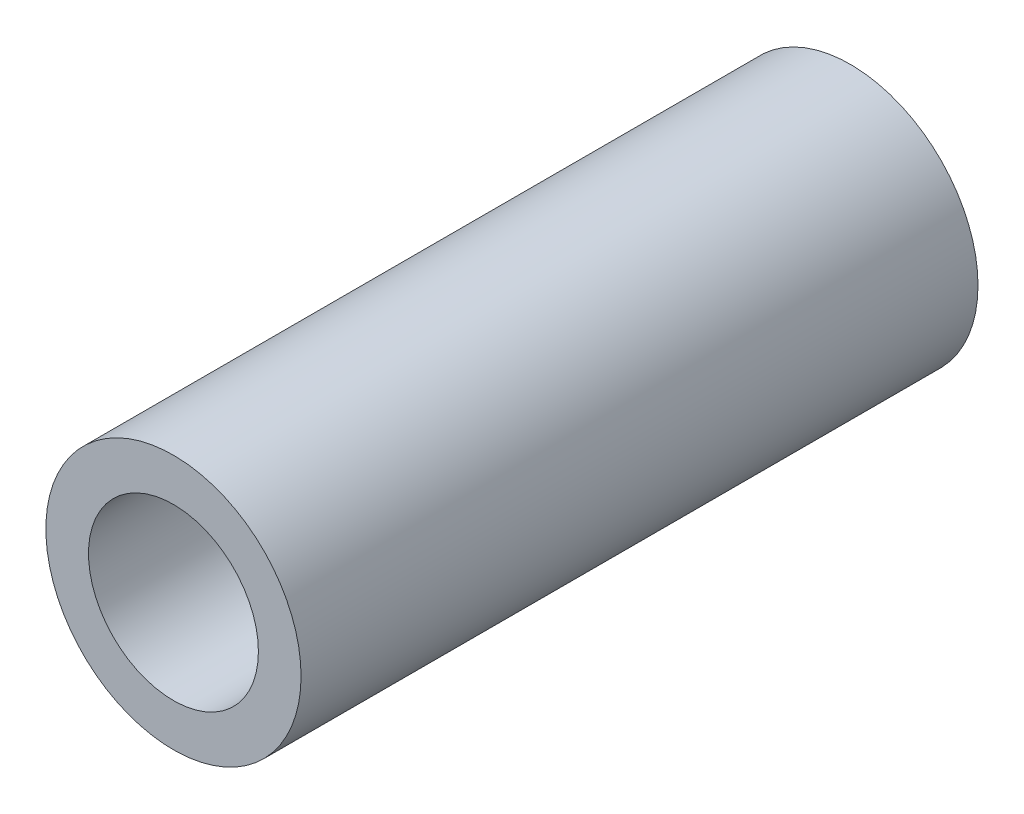
SolidWorks part; units mm, degrees
ref_plane "Front Plane" through (0, 0, 0) normal (0, 0, 1) x (1, 0, 0)
ref_plane "Top Plane" through (0, 0, 0) normal (0, 1, 0) x (1, 0, 0)
ref_plane "Right Plane" through (0, 0, 0) normal (1, 0, 0) x (0, 0, -1)
sketch "Sketch1" plane through (0, 0, 0) normal (0, 0, 1) x (1, 0, 0)
  circle A0 centre (0, 0) radius 2.394
  circle A1 centre (0, 0) radius 1.5939
  dimension "OD" = 4.7879
  dimension "ID" = 3.1877
sketch "Sketch2" plane through (0, 0, 0) normal (1, 0, 0) x (0, 0, -1)
  line L2 (6.35, 0) -> (-6.35, 0) construction
  line L4 (-6.35, -2.394) -> (-6.35, 2.3939) construction
  line L5 (-6.35, -1.5938) -> (6.35, -1.5938)
  line L6 (6.35, 1.5938) -> (-6.35, 1.5938)
  line L7 (6.35, -2.3939) -> (6.35, 2.3939) construction
  line L8 (-6.35, 2.3939) -> (6.35, 2.3939) construction
  line L9 (-6.35, -2.394) -> (6.35, -2.3939) construction
  line L10 (0, 2.394) -> (0, -2.394) construction
  line L11 (0, 1.5938) -> (0, -1.5938) construction
  point P4 (0, -1.5938)
  point P7 (0, 1.5938)
  point P8 (0, 0)
  point P12 (-6.35, 0)
  point P15 (6.35, 0)
  point P16 (0, -2.394)
  point P17 (0, 2.394)
  dimension "Length" = 12.7
sketch "Sketch5" plane through (0, 0, 0) normal (0, 0, 1) x (1, 0, 0)
  circle A1 centre (0, 0) radius 1.5939
  circle A2 centre (0, 0) radius 1.5939
  circle A3 centre (0, 0) radius 2.394
  circle A4 centre (0, 0) radius 2.394
  dimension "D1" = 0
  dimension "D2" = 0
extrude "Boss-Extrude1" add sketch "Sketch5" along normal up to vertex and the other way up to vertex up to point (0, 0, 6.35) other way up to point (0, 0, -6.35)
sketch "Sketch4" plane through (0, 0, 6.35) normal (0, 0, 1) x (1, 0, 0)
  line L0 (0, 0) -> (-1.127, 1.127)
  line L2 (0, -2.394) -> (0, 2.3939) construction
  circle A1 centre (0, 0) radius 1.5939 construction
  dimension "D1" = 45
equation "\"D1\"= \"Length@Sketch2\""
